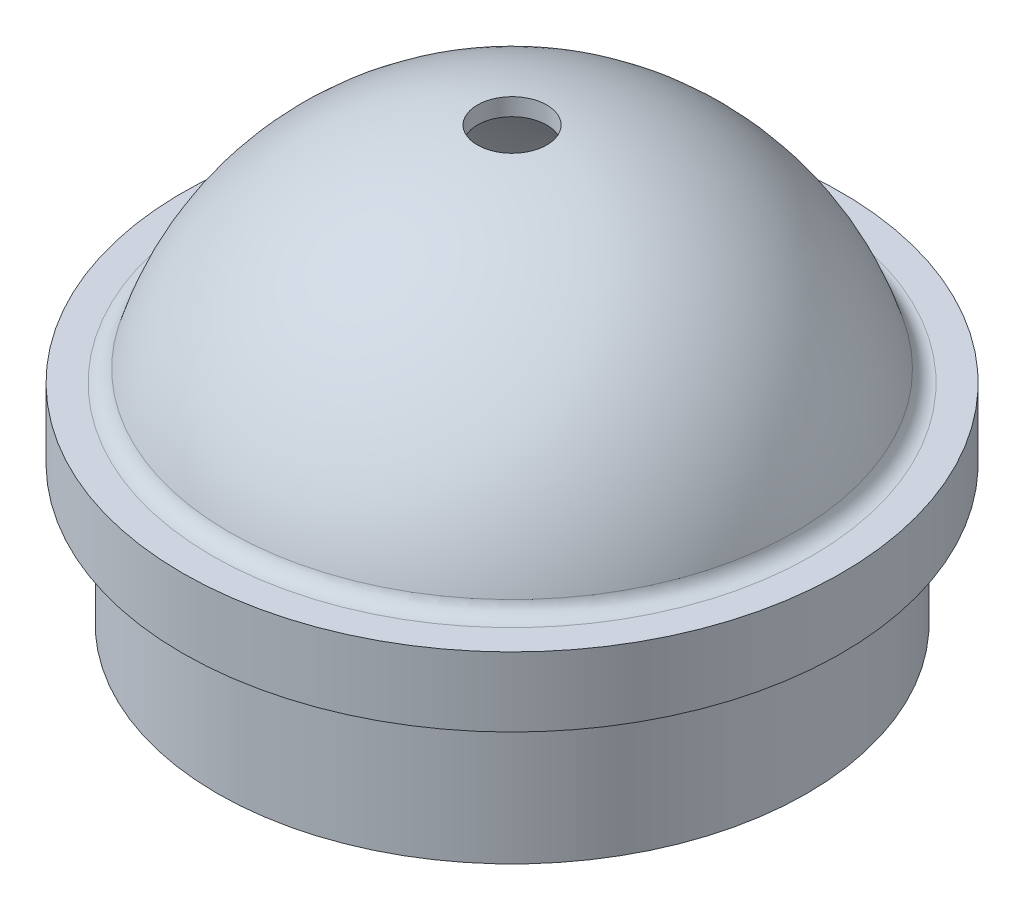
SolidWorks part; units mm, degrees
material "6061-T6 (SS)"
ref_plane "Front Plane" through (0, 0, 0) normal (0, 0, 1) x (1, 0, 0)
ref_plane "Top Plane" through (0, 0, 0) normal (0, 1, 0) x (1, 0, 0)
ref_plane "Right Plane" through (0, 0, 0) normal (1, 0, 0) x (0, 0, -1)
ref_axis "Axis1" through (0, 121.2368, 0) along (0, -1, 0)
sketch "Sketch1" plane through (0, 0, 0) normal (0, 0, 1) x (1, 0, 0)
  line L0 (-53.975, 0) -> (-53.975, 25.4)
  line L1 (91.7825, 0) -> (-91.7825, 0) construction
  line L2 (-53.975, 25.4) -> (-60.325, 25.4)
  line L3 (-6.35, 78.9766) -> (-6.35, 75.8016)
  line L4 (-50.8, 25.4) -> (-50.8, 0)
  line L5 (-53.975, 0) -> (-50.8, 0)
  line L6 (0, 121.2368) -> (0, -54.1879) construction
  line L7 (-54.8765, 38.1) -> (-60.325, 38.1)
  line L8 (-60.325, 25.4) -> (-60.325, 38.1)
  arc A0 (-51.8265, 40.3927) -> (-6.35, 78.9766) centre (0, 25.4) cw
  arc A1 (-53.9516, 25.4) -> (-6.35, 78.9766) centre (0, 25.4) cw construction
  arc A2 (-50.8, 25.4) -> (-6.35, 75.8016) centre (0, 25.4) cw
  arc A3 (-51.8265, 40.3927) -> (-54.8765, 38.1) centre (-54.8765, 41.275) cw
  arc A5 (-50.8, 25.4) -> (-5.9791, 75.8469) centre (0, 25.4) cw construction
  point P23 (-53.975, 25.4)
  dimension "D1" = 6.35
  dimension "D8" = 25.4
  dimension "D9" = 3.175
  dimension "D10" = 6.35
  dimension "D5" = 3.175
  dimension "D2" = 50.8
  dimension "D3" = 50.8
  dimension "D7" = 12.7
  dimension "D4" = 3.175
revolve "Revolve7" add sketch "Sketch1" angle 360 about axis through (0, 121.2368, 0) along (0, -1, 0)
